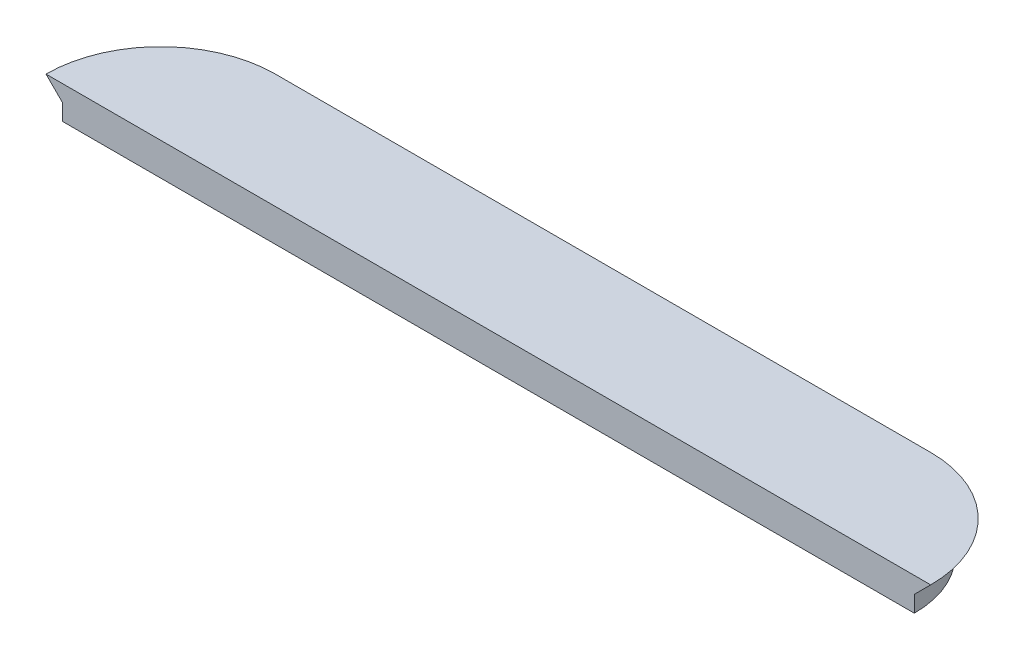
SolidWorks part; units mm, degrees
ref_plane "Front Plane" through (0, 0, 0) normal (0, 0, 1) x (1, 0, 0)
ref_plane "Top Plane" through (0, 0, 0) normal (0, 1, 0) x (1, 0, 0)
ref_plane "Right Plane" through (0, 0, 0) normal (1, 0, 0) x (0, 0, -1)
sketch "Sketch1" plane through (0, 0, 0) normal (0, 1, 0) x (1, 0, 0)
  line L0 (0, 0) -> (-8.75, 0)
  line L1 (0, 0) -> (50, 0)
  line L3 (0, 8.75) -> (50, 8.75)
  line L6 (50, 0) -> (58.75, 0)
  arc A0 (0, 8.75) -> (-8.75, 0) centre (0, 0) ccw
  arc A1 (50, 8.75) -> (58.75, 0) centre (50, 0) cw
  dimension "D1" = 50
  dimension "D2" = 8.75
extrude "Boss-Extrude1" add sketch "Sketch1" along normal blind 2.5
sketch "Sketch3" plane through (0, 0, 0) normal (0, -1, 0) x (1, 0, 0)
  line L0 (-8.75, 0) -> (-7.5, 0)
  line L1 (-8.75, 0) -> (58.75, 0) construction
  line L2 (0, -8.75) -> (0, -7.5)
  line L3 (50, -8.75) -> (50, -7.5)
  line L4 (58.75, 0) -> (57.5, 0)
  line L5 (0, -7.5) -> (50, -7.5)
  arc A0 (-7.5, 0) -> (0, -7.5) centre (0, 0) ccw
  arc A1 (50, -7.5) -> (57.5, 0) centre (50, 0) ccw
  arc M3 (50, -8.75) -> (58.75, 0) centre (50, 0) ccw
  line M4 (58.75, 0) -> (-8.75, 0)
  arc M5 (-8.75, 0) -> (0, -8.75) centre (0, 0) ccw
  line M6 (0, -8.75) -> (50, -8.75)
extrude "Cut-Extrude2" cut sketch "Sketch3" against normal blind 1.25 contours A1 L3 M3 M4 | L5 L2 L3 M6 | A0 L2 M4 M5 region at (-8.125, 0, -0.1237) region at (25, 0, -8.125) region at (58.125, 0, -0.1237)
chamfer "Chamfer2" distance 1.25 angle 45 3 edges at (56.1872, 1.25, -6.1872) (25, 1.25, -8.75) (-6.1872, 1.25, -6.1872)
